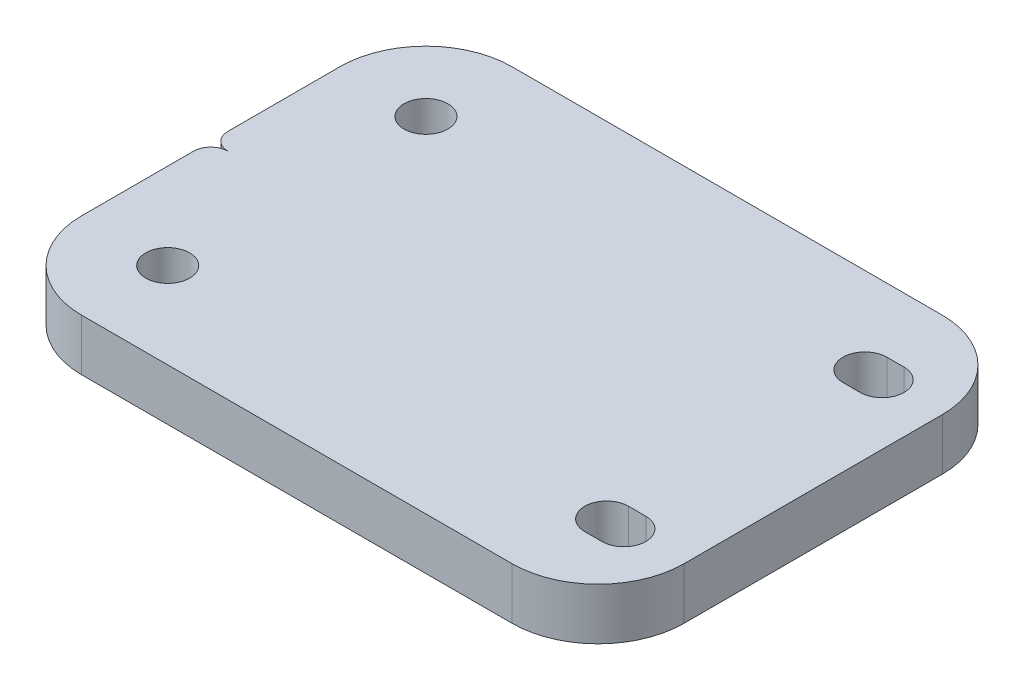
SolidWorks part; units mm, degrees
material "Клен"
ref_plane "Спереди" through (0, 0, 0) normal (0, 0, 1) x (1, 0, 0)
ref_plane "Сверху" through (0, 0, 0) normal (0, 1, 0) x (1, 0, 0)
ref_plane "Справа" through (0, 0, 0) normal (1, 0, 0) x (0, 0, -1)
sketch "Эскиз1" plane through (0, 0, 0) normal (0, 1, 0) x (1, 0, 0)
  line L0 (-41.181, -0.0464) -> (44.1026, -0.0464) construction
  line L10 (-25, -25) -> (25, -25)
  line L11 (-35, -15) -> (-35, 15)
  line L12 (-25, 25) -> (25, 25)
  line L13 (35, -15) -> (35, 15)
  line L14 (-35, -25) -> (35, 25) construction
  line L15 (-35, 25) -> (35, -25) construction
  arc A4 (25, 25) -> (35, 15) centre (25, 15) cw
  arc A5 (25, -25) -> (35, -15) centre (25, -15) ccw
  arc A6 (-25, -25) -> (-35, -15) centre (-25, -15) cw
  arc A7 (-35, 15) -> (-25, 25) centre (-25, 15) cw
  point P0 (0, 0)
  dimension "D1" = 10
  dimension "D2" = 50
  dimension "D3" = 70
extrude "Бобышка-Вытянуть1" add sketch "Эскиз1" along normal blind 6
sketch "Эскиз2" plane through (0, 0, 0) normal (0, -1, 0) x (1, 0, 0)
  line L0 (0, -37.0349) -> (0, 29.2907) construction
  line L1 (28, -15) -> (26, -15) construction
  line L2 (28, -17.55) -> (26, -17.55)
  line L3 (28, -12.45) -> (26, -12.45)
  line L6 (-46.1924, 0) -> (55.6646, 0) construction
  line L7 (28, 15) -> (26, 15) construction
  line L8 (28, 17.55) -> (26, 17.55)
  line L9 (28, 12.45) -> (26, 12.45)
  line L10 (-35, -15) -> (-35, 15) construction
  line L11 (25, -25) -> (-25, -25) construction
  circle A0 centre (-25, -15) radius 2.55
  arc A1 (28, -17.55) -> (28, -12.45) centre (28, -15) ccw
  arc A2 (26, -12.45) -> (26, -17.55) centre (26, -15) ccw
  arc A3 (28, 17.55) -> (28, 12.45) centre (28, 15) cw
  arc A4 (26, 12.45) -> (26, 17.55) centre (26, 15) cw
  circle A5 centre (-25, 15) radius 2.55
  point P7 (27, -15)
  point P12 (27, -17.55)
  point P21 (27, 15)
  dimension "D1" = 5.1
  dimension "D2" = 5.1
  dimension "D3" = 2
  dimension "D4" = 53
  dimension "D5" = 10
  dimension "D6" = 10
extrude "Вырез-Вытянуть1" cut sketch "Эскиз2" against normal through all
sketch "Эскиз3" plane through (0, 0, 0) normal (0, -1, 0) x (1, 0, 0)
  line L0 (-33, 0) -> (27.7687, 0) construction
  line L1 (-35, -15) -> (-35, 15) construction
  line L2 (-35, -2) -> (-35, 2)
  arc A0 (-33, 0) -> (-35, -2) centre (-33, -2) ccw
  arc A1 (-33, 0) -> (-35, 2) centre (-33, 2) cw
  point P3 (-35, -2)
  point P4 (-33, 0)
  point P7 (-35, 2)
  dimension "D2" = 2
  dimension "D1" = 2
extrude "Вырез-Вытянуть2" cut sketch "Эскиз3" against normal through all
equation "\"D2@Эскиз2\"=\"D1@Эскиз2\""
